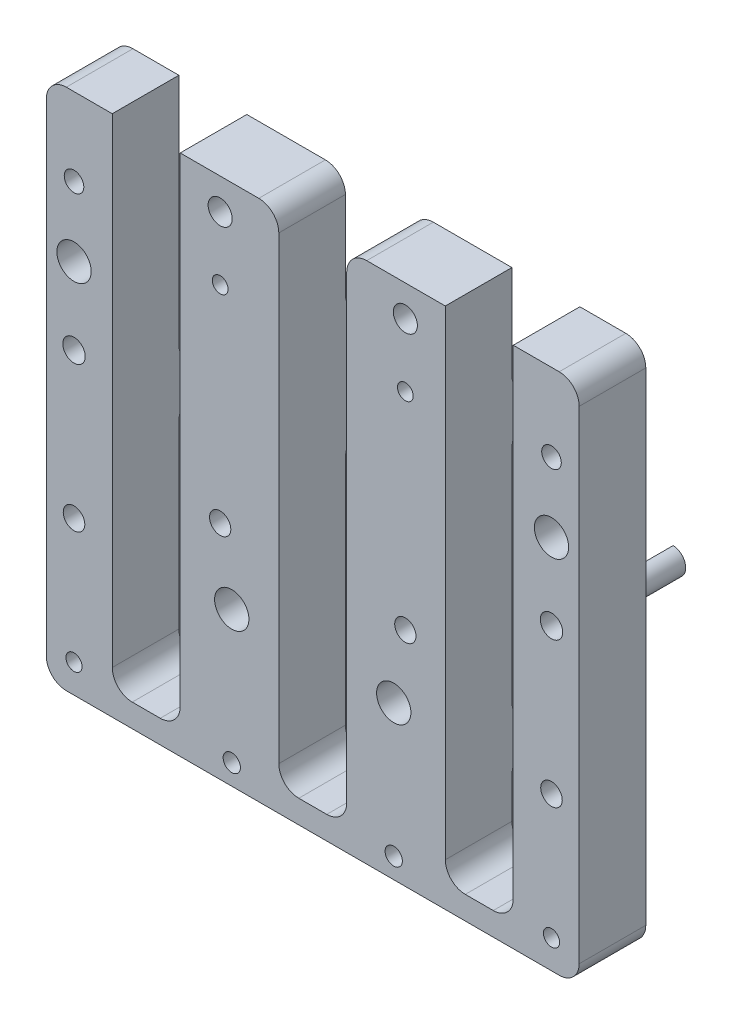
SolidWorks part; units mm, degrees
material "Polyol polyéther"
ref_plane "Plan de face" through (0, 0, 0) normal (0, 0, 1) x (1, 0, 0)
ref_plane "Plan de dessus" through (0, 0, 0) normal (0, 1, 0) x (1, 0, 0)
ref_plane "Plan de droite" through (0, 0, 0) normal (1, 0, 0) x (0, 0, -1)
sketch "Esquisse1" plane through (0, 0, 0) normal (0, 0, 1) x (1, 0, 0)
  line L0 (0, 16.8352) -> (0, -15.5073) construction
  line L1 (-15.2, 0) -> (15.4353, 0) construction
  circle A0 centre (0, 30.04) radius 1.95
  circle A1 centre (21.2418, 21.2422) radius 1.95
  circle A2 centre (30.041, 0.001) radius 1.95
  circle A3 centre (21.2432, -21.2408) radius 1.95
  circle A4 centre (0.002, -30.04) radius 1.95
  circle A5 centre (-21.2398, -21.2422) radius 1.95
  circle A6 centre (-30.039, -0.001) radius 1.95
  circle A7 centre (-21.2412, 21.2408) radius 1.95
  point P7 (0, 0)
  point P24 (0.001, 0)
  dimension "D1" = 3.9
  dimension "D2" = 30.04
  dimension "D3" = 8
extrude "Boss.-Extru.1" add sketch "Esquisse1" along normal blind 24
sketch "Esquisse2" plane through (0, 0, 24) normal (0, 0, 1) x (1, 0, 0)
  line L0 (-40, 0) -> (-40, 40)
  line L1 (-40, 40) -> (0, 40)
  line L2 (40, 0) -> (40, 40)
  line L3 (40, 40) -> (0, 40)
  line L4 (-40, 0) -> (-40, -38.4697)
  line L5 (-40, -38.4697) -> (40, -38.4697)
  line L6 (40, -38.4697) -> (40, 0)
extrude "Boss.-Extru.2" add sketch "Esquisse2" against normal blind 10
sketch "Esquisse3" plane through (0, 0, 24) normal (0, 0, 1) x (1, 0, 0)
  line L0 (0, 0) -> (0, 40.8596) construction
  line L1 (5.1, 40) -> (5.1, -35)
  line L2 (40, 40) -> (-40, 40) construction
  line L3 (5.1, -35) -> (-5.1, -35)
  line L4 (-5.1, -35) -> (-5.1, 40)
  line L5 (5.1, 40) -> (-5.1, 40)
  line L6 (30.1, 40) -> (19.9, 40)
  line L7 (19.9, -35) -> (19.9, 40)
  line L8 (30.1, -35) -> (19.9, -35)
  line L9 (30.1, 40) -> (30.1, -35)
  line L10 (-19.9, 40) -> (-30.1, 40)
  line L11 (-30.1, -35) -> (-30.1, 40)
  line L12 (-19.9, -35) -> (-30.1, -35)
  line L13 (-19.9, 40) -> (-19.9, -35)
  dimension "D1" = 5.1
  dimension "D2" = 5.1
  dimension "D3" = 75
  dimension "D4" = 2
  dimension "D5" = 2
extrude "Enlèv. mat.-Extru.1" cut sketch "Esquisse3" against normal through all
sketch "Esquisse4" plane through (0, 0, 14) normal (0, 0, -1) x (-1, 0, 0)
  line L0 (5.1, 40) -> (5.1, -35) construction
  line L1 (8.5401, 5.7711) -> (5.1, 5.7711)
  line L2 (8.5401, 5.7711) -> (8.5401, 21.0079)
  line L3 (8.5401, 21.0079) -> (5.1, 21.0079)
  line L4 (5.1, 5.7711) -> (5.1, 21.0079)
  line L5 (0, -35) -> (0, 31.5698) construction
  line L6 (5.1, -35) -> (-5.1, -35) construction
  line L7 (-8.5401, 21.0079) -> (-5.1, 21.0079)
  line L8 (-5.1, 5.7711) -> (-5.1, 21.0079)
  line L9 (-8.5401, 5.7711) -> (-5.1, 5.7711)
  line L10 (-8.5401, 5.7711) -> (-8.5401, 21.0079)
extrude "Boss.-Extru.3" add sketch "Esquisse4" along normal blind 5.75
sketch "Esquisse5" plane through (0, 0, 8.25) normal (0, 0, -1) x (-1, 0, 0)
  line L1 (8.5401, 5.7711) -> (-8.5401, 5.7711)
  line L2 (8.5401, 5.7711) -> (8.5401, 21.0079)
  line L3 (8.5401, 21.0079) -> (-8.5401, 21.0079)
  line L4 (-8.5401, 5.7711) -> (-8.5401, 21.0079)
extrude "Boss.-Extru.4" add sketch "Esquisse5" along normal blind 3
fillet "Congé1" radius 3 3 edges at (6.82, 5.7711, 14) (8.5401, 13.3895, 14) (6.82, 21.0079, 14)
fillet "Congé2" radius 3 3 edges at (-6.82, 5.7711, 14) (-8.5401, 13.3895, 14) (-6.82, 21.0079, 14)
fillet "Congé3" radius 3 6 edges at (-19.2912, 21.2408, 14) (-31.989, -0.001, 14) (-19.2898, -21.2422, 14) (19.2932, -21.2408, 14) (31.991, 0.001, 14) (19.2918, 21.2422, 14)
fillet "Congé4" radius 3 4 edges at (40, 40, 19) (5.1, 40, 19) (-5.1, 40, 19) (-40, 40, 19)
fillet "Congé5" radius 2 8 edges at (9.4187, 4.8925, 13.1213) (-9.4187, 4.8925, 13.1213) (-9.4187, 21.8866, 13.1213) (9.4187, 21.8866, 13.1213) (8.5401, 5.7711, 8.125) (-8.5401, 5.7711, 8.125) (-8.5401, 21.0079, 8.125) (8.5401, 21.0079, 8.125)
sketch "Esquisse6" plane through (0, 0, 14) normal (0, 0, -1) x (-1, 0, 0)
  line L0 (0, -40) -> (0, 48.2912) construction
  circle A6 centre (12.1576, -15.4738) radius 2.5746
  circle A7 centre (35.8425, 17.8967) radius 2.5724
  circle A9 centre (13.8997, 35.3395) radius 1.8081
  circle A10 centre (13.8997, 25.865) radius 1.1848
  circle A12 centre (35.8425, 6.3863) radius 1.6817
  circle A14 centre (35.8425, 28.3239) radius 1.4693
  circle A15 centre (35.8425, -34.1725) radius 1.2127
  circle A16 centre (35.8425, -15.4738) radius 1.6178
  circle A17 centre (13.8997, -5.1373) radius 1.5954
  circle A18 centre (12.1576, -35.3979) radius 1.2973
  arc A19 (-19.9, -34.6986) -> (19.9, -34.6986) centre (0, 0) ccw construction
  circle A21 centre (-13.8997, 25.865) radius 1.1848
  circle A22 centre (-13.8997, 35.3395) radius 1.8081
  circle A24 centre (-35.8425, 28.3239) radius 1.4693
  circle A25 centre (-35.8425, -34.1725) radius 1.2127
  circle A27 centre (-35.8425, 17.8967) radius 2.5724
  circle A28 centre (-35.8425, 6.3863) radius 1.6817
  circle A29 centre (-35.8425, -15.4738) radius 1.6178
  circle A32 centre (-12.1576, -35.3979) radius 1.2973
  circle A34 centre (-12.1576, -15.4738) radius 2.5746
  circle A35 centre (-13.8997, -5.1373) radius 1.5954
  point P0 (13.8997, 25.865)
extrude "Enlèv. mat.-Extru.2" cut sketch "Esquisse6" against normal through all
fillet "Congé6" radius 3 6 edges at (-30.1, -35, 19) (-19.9, -35, 19) (-5.1, -35, 19) (5.1, -35, 19) (19.9, -35, 19) (30.1, -35, 19)
fillet "Congé7" radius 3 2 edges at (-40, -38.4697, 19) (40, -38.4697, 19)
